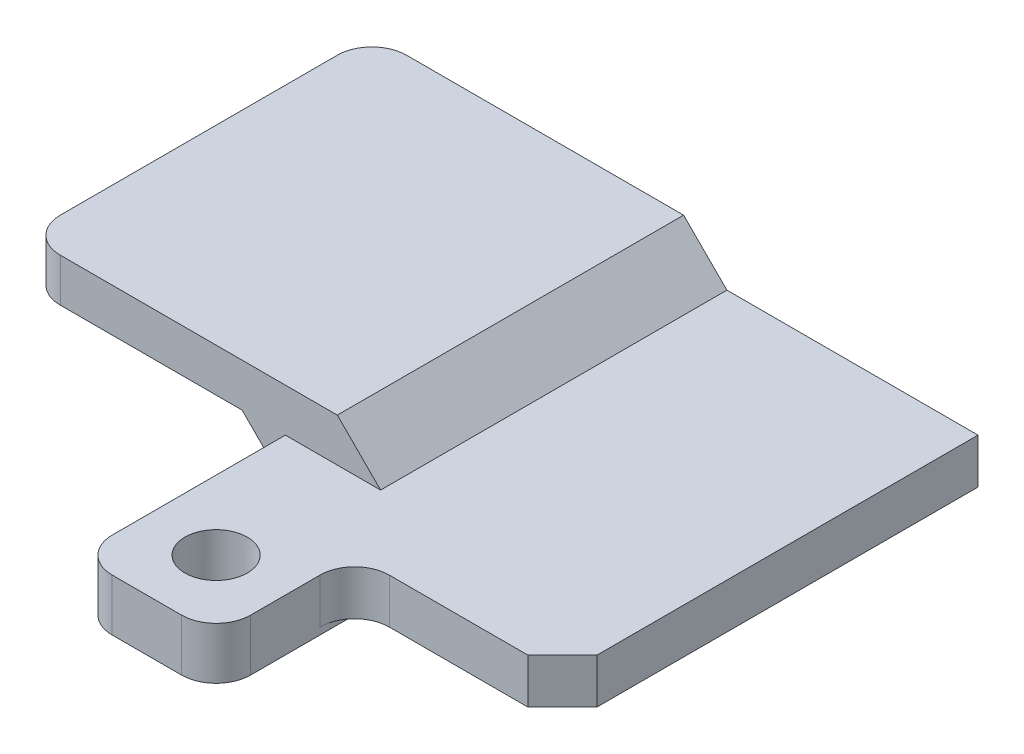
SolidWorks part; units mm, degrees
ref_plane "Płaszczyzna przednia" through (0, 0, 0) normal (0, 0, 1) x (1, 0, 0)
ref_plane "Płaszczyzna górna" through (0, 0, 0) normal (0, 1, 0) x (1, 0, 0)
ref_plane "Płaszczyzna prawa" through (0, 0, 0) normal (1, 0, 0) x (0, 0, -1)
sketch "Sketch1" plane through (0, 0, 0) normal (0, 1, 0) x (1, 0, 0)
  line L1 (0, 0) -> (20, 0)
  line L2 (0, 0) -> (0, 24)
  line L3 (0, 24) -> (20, 24)
  line L4 (20, 0) -> (20, 24)
  dimension "D1" = 24
  dimension "D2" = 20
extrude "Boss-Extrude1" add sketch "Sketch1" along normal blind 3
sketch "Sketch2" plane through (0, 3, 0) normal (0, 1, 0) x (1, 0, 0)
  line L0 (0, 24) -> (0, 0) construction
  line L1 (0, -8) -> (8, -8)
  line L2 (0, -8) -> (0, 0)
  line L3 (0, 0) -> (8, 0)
  line L4 (8, -8) -> (8, 0)
  line L5 (0, -8) -> (8, 0) construction
  line L6 (0, 0) -> (8, -8) construction
  line L7 (0, 0) -> (20, 0) construction
  circle A0 centre (4, -4) radius 1.8
  point P0 (4, -4)
  dimension "D2" = 3.6
  dimension "D1" = 8
extrude "Boss-Extrude2" add sketch "Sketch2" against normal up to surface (3 mm away) up to face at (10, 0, -12)
fillet "Fillet1" radius 2 3 edges at (8, 1.5, 0) (8, 1.5, 8) (0, 1.5, 8)
chamfer "Chamfer1" distance 2 angle 45 1 edges at (20, 1.5, 0)
sketch "Sketch3" plane through (0, 3, 0) normal (0, 1, 0) x (1, 0, 0)
  line L0 (20, 24) -> (0, 24) construction
  line L1 (3, 24) -> (-15, 24)
  line L2 (3, 24) -> (3, 0)
  line L3 (3, 0) -> (-15, 0)
  line L4 (-15, 24) -> (-15, 0)
  line L5 (10, 0) -> (18, 0) construction
  line L6 (0, 24) -> (0, -6) construction
  dimension "D1" = 18
  dimension "D2" = 3
extrude "Boss-Extrude3" add sketch "Sketch3" along normal blind 2.5
chamfer "Chamfer2" distance 2.5 angle 45 2 edges at (0, 3, -12) (3, 3, -12)
sketch "Sketch5" plane through (0, 0, 0) normal (0, 0, 1) x (1, 0, 0)
  line L7 (-15, 3) -> (-2.5, 3)
  line L8 (-2.5, 3) -> (0, 0.5)
  line L9 (0, 0.5) -> (0, 3)
  line L10 (0, 3) -> (5.5, 3)
  line L11 (5.5, 3) -> (3, 5.5)
  line L12 (3, 5.5) -> (-15, 5.5)
  line L13 (-15, 5.5) -> (-15, 3)
  line L14 (-15, 3) -> (-2.5, 3)
  line L15 (-2.5, 3) -> (0, 0.5)
  line L16 (0, 0.5) -> (0, 3)
  line L17 (0, 3) -> (5.5, 3)
  line L18 (5.5, 3) -> (3, 5.5)
  line L19 (3, 5.5) -> (-15, 5.5)
  line L20 (-15, 5.5) -> (-15, 3)
  dimension "D1" = 0
extrude "Cut-Extrude4" cut sketch "Sketch5" against normal blind 4
fillet "Fillet2" radius 2 2 edges at (-15, 4.25, -24) (-15, 4.25, -4)
sketch "Sketch4" plane through (0, 0, 0) normal (0, -1, 0) x (1, 0, 0)
  line L0 (8, 2) -> (8, 0)
  line L1 (0, 0) -> (8, 0)
  line L2 (0, 0) -> (0, -24)
  line L3 (0, -24) -> (20, -24)
  line L4 (20, 0) -> (20, -24)
  line L5 (8, 2) -> (20, 2)
  line L6 (20, 2) -> (20, 0)
  line M1 (20, -24) -> (20, -2)
  line M2 (20, -2) -> (18, 0)
  line M3 (18, 0) -> (10, 0)
  line M9 (0, 6) -> (0, -24)
  line M10 (0, -24) -> (20, -24)
extrude "Cut-Extrude3" cut sketch "Sketch4" against normal blind 0.4 contours L1 M9 M10 M1 M2 M3 region at (10.1905, 0, -11.381)
